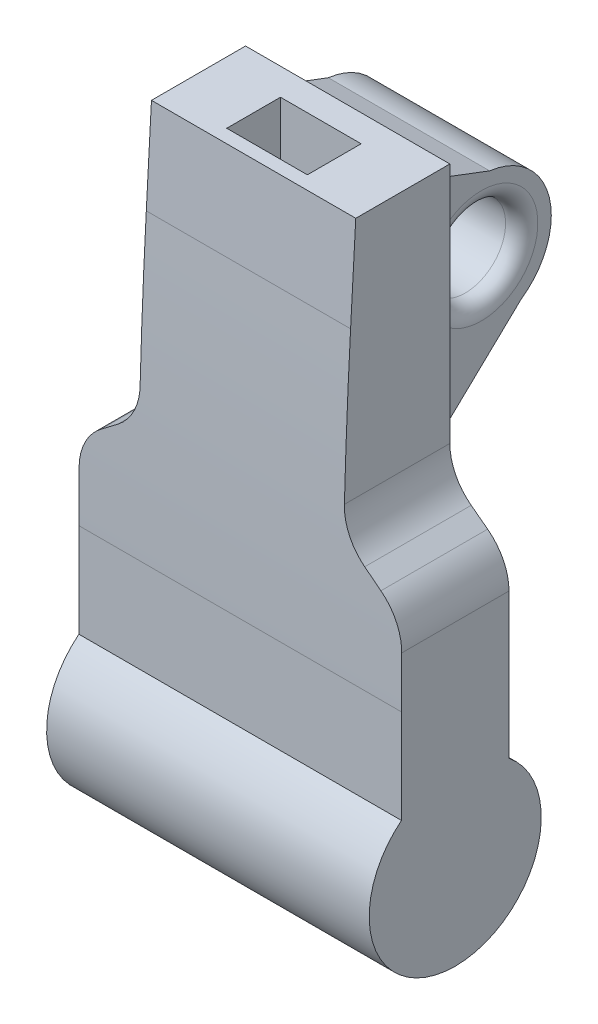
SolidWorks part; units mm, degrees
ref_plane "Front Plane" through (0, 0, 0) normal (0, 0, 1) x (1, 0, 0)
ref_plane "Top Plane" through (0, 0, 0) normal (0, 1, 0) x (1, 0, 0)
ref_plane "Right Plane" through (0, 0, 0) normal (1, 0, 0) x (0, 0, -1)
sketch "Sketch2" plane through (0, 0, 0) normal (1, 0, 0) x (0, 0, -1)
  circle A0 centre (0, 0) radius 16
extrude "Boss-Extrude1" add sketch "Sketch2" along normal blind 60 contours A0
sketch "Sketch3" plane through (0, 0, 0) normal (1, 0, 0) x (0, 0, -1)
  circle A0 centre (0, 0) radius 3.75
extrude "Cut-Extrude1" cut sketch "Sketch3" along normal blind 8.5
sketch "Sketch4" plane through (0, 0, 0) normal (1, 0, 0) x (0, 0, -1)
  line L0 (4.9329, 12.49) -> (10, 12.49)
  line L1 (10, 12.49) -> (-10, 12.49)
  line L2 (-10, 12.49) -> (-10, 15.8222)
  line L5 (10, 12.49) -> (10, 22.7394)
  line L6 (10, 22.7394) -> (-10, 22.7394)
  line L7 (-10, 22.7394) -> (-10, 15.8222)
  circle A0 centre (0, 0) radius 16 construction
extrude "Boss-Extrude3" add sketch "Sketch4" along normal through all contours L5 L6 L7 L2 L1
sketch "Sketch5" plane through (0, 0, 0) normal (1, 0, 0) x (0, 0, -1)
  line L0 (10, 22.7394) -> (10, 102.7394)
  line L2 (-10, 22.7394) -> (-10, 102.7394)
  line L3 (-10, 102.7394) -> (10, 102.7394)
  line L4 (10, 22.7394) -> (-10, 22.7394)
  dimension "D1" = 80
extrude "Boss-Extrude4" add sketch "Sketch5" along normal blind 60
ref_plane "Plane1" through (30, 0, 0) normal (1, 0, 0) x (0, 0, -1)
sketch "Sketch8" plane through (30, 0, 0) normal (1, 0, 0) x (0, 0, -1)
  circle A0 centre (19.8694, 81.0137) radius 7.5
  circle A1 centre (19.8694, 81.0137) radius 13
extrude "Boss-Extrude5" add sketch "Sketch8" along normal blind 15 and the other way blind 15
sketch "Sketch9" plane through (30, 0, 0) normal (1, 0, 0) x (0, 0, -1)
  line L29 (10, 53.862) -> (30.2106, 73.1358)
  line L30 (10, 12.49) -> (10, 102.7394) construction
  line L31 (30.2106, 73.1358) -> (27.5485, 88.9988)
  line L32 (27.5485, 88.9988) -> (27.5485, 75.9273)
  line L33 (27.5485, 75.9273) -> (23.4279, 71.9976)
  line L34 (23.4279, 71.9976) -> (12.9082, 73.9624)
  line L35 (12.9082, 73.9624) -> (11.7158, 81.0673)
  line L36 (11.7158, 81.0673) -> (12.8618, 87.2025)
  line L37 (12.8618, 87.2025) -> (20.1053, 90.4629)
  line L38 (20.1053, 90.4629) -> (21.4167, 93.9213)
  line L39 (21.4167, 93.9213) -> (10, 98.2506)
  line L40 (10, 98.2506) -> (4.6568, 69.6434)
  line L41 (4.6568, 69.6434) -> (10, 53.862)
  arc A3 (10, 72.5523) -> (10, 89.475) centre (19.8694, 81.0137) ccw construction
extrude "Boss-Extrude6" add sketch "Sketch9" along normal blind 15 and the other way blind 15
fillet "Fillet5" radius 3 2 edges at (15, 81.0137, -27.3694) (45, 81.0137, -27.3694)
sketch "Sketch10" plane through (0, 0, 0) normal (0, 0, 1) x (1, 0, 0)
  line L0 (0, 12.49) -> (0, 30.4374)
  line L1 (60, 44.4271) -> (49, 52.7394)
  line L2 (15, 53.862) -> (45, 53.862)
  line L3 (49, 52.7394) -> (49, 102.7394)
  line L4 (60, 30.4374) -> (60, 12.49)
  line L5 (60, 12.49) -> (60, 102.7394) construction
  line L6 (60, 12.49) -> (0, 12.49) construction
  line L7 (0, 12.49) -> (0, 102.7394) construction
  line L8 (60, 102.7394) -> (0, 102.7394) construction
  line L9 (49, 102.7394) -> (11, 102.7394)
  line L10 (11, 102.7394) -> (11, 52.7394)
  line L11 (11, 52.7394) -> (0, 44.4271)
  line L12 (0, 44.4271) -> (0, 30.4374)
  line L13 (60, 44.4271) -> (60, 107.7059)
  line L14 (60, 107.7059) -> (1.126, 107.7059)
  line L15 (1.126, 107.7059) -> (-1.6394, 104.9405)
  line L16 (-1.6394, 104.9405) -> (-2.7781, 42.475)
  line L17 (-2.7781, 42.475) -> (0, 44.4271)
  dimension "D1" = 11
  dimension "D2" = 11
  dimension "D3" = 50
  dimension "D4" = 50
  dimension "D5" = 13.7875
  dimension "D6" = 13.7875
extrude "Cut-Extrude2" cut sketch "Sketch10" against normal through all both and the other way through all contours L11 L10 L9 L3 L1 L13 L14 L15 L16 L17
sketch "Sketch11" plane through (0, 0, 0) normal (0, 0, 1) x (1, 0, 0)
  line L0 (30, 102.8258) -> (30, 82.7394)
  line L1 (30, -26.8782) -> (30, 26.8782) construction
  line L2 (30, 82.7394) -> (22.5, 82.7394)
  line L3 (22.5, 82.7394) -> (37.5, 82.7394)
  line L4 (37.5, 82.7394) -> (37.5, 102.7394)
  line L5 (49, 102.7394) -> (11, 102.7394) construction
  line L6 (37.5, 102.7394) -> (22.5, 102.7394)
  line L7 (22.5, 102.7394) -> (22.5, 82.7394)
  dimension "D1" = 15
  dimension "D2" = 7.5
  dimension "D3" = 7.5
  dimension "D4" = 20
fillet "Fillet6" radius 10 4 edges at (60, 44.4271, 0) (49, 52.7394, 0) (11, 52.7394, 0) (0, 44.4271, 0)
extrude "Cut-Extrude3" cut sketch "Sketch11" against normal blind 5 and the other way blind 5 contours L3 L4 L6 L7
sketch "Sketch13" plane through (30, 0, 0) normal (1, 0, 0) x (0, 0, -1)
  line L0 (-10, 102.7394) -> (-7.5, 102.7394)
  line L1 (10, 102.7394) -> (-10, 102.7394) construction
  line L2 (-7.5, 102.7394) -> (-10, 57.7168)
  line L3 (-10, 57.7168) -> (-10, 102.7394)
extrude "Cut-Extrude4" cut sketch "Sketch13" against normal through all both and the other way through all
fillet "Fillet7" radius 1000 1 edges at (30, 57.7168, 10)
